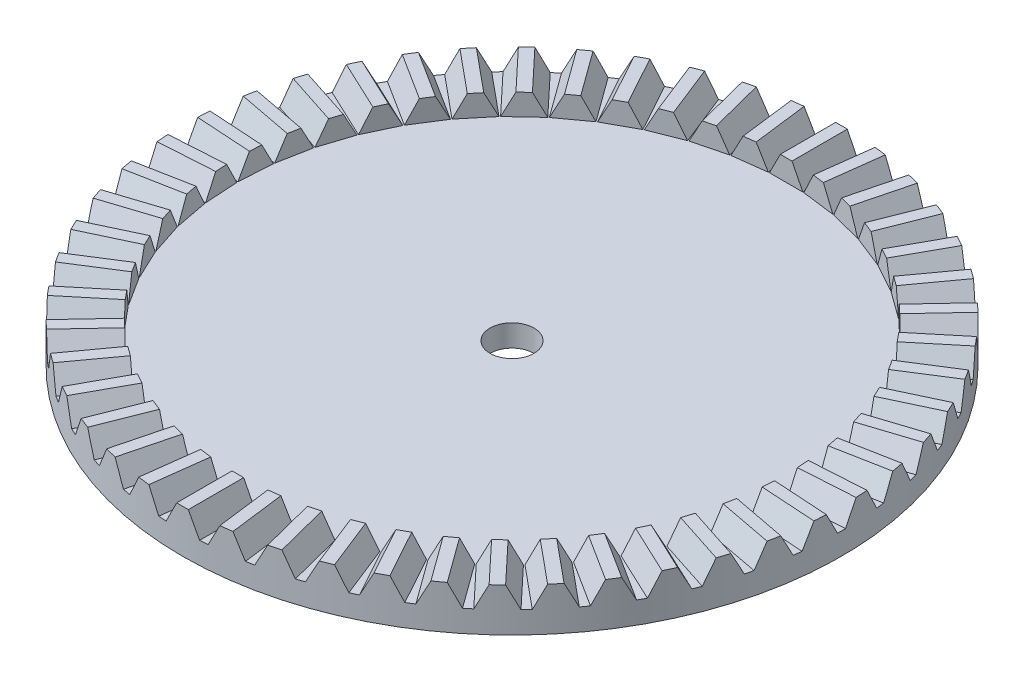
SolidWorks part; units mm, degrees
ref_plane "Front Plane" through (0, 0, 0) normal (0, 0, 1) x (1, 0, 0)
ref_plane "Top Plane" through (0, 0, 0) normal (0, 1, 0) x (1, 0, 0)
ref_plane "Right Plane" through (0, 0, 0) normal (1, 0, 0) x (0, 0, -1)
sketch "Foot Measurements" [suppressed] plane through (0, 0, 0) normal (0, 1, 0) x (1, 0, 0)
  line L0 (0, 0) -> (0, 73) construction
  line L1 (0, 0) -> (0, 147) construction
  line L2 (0, 0) -> (33, 0) construction
  line L3 (0, 0) -> (75, 0) construction
  line L4 (0, 73) -> (33, 73) construction
  line L5 (33, 73) -> (33, 0) construction
  line L6 (0, 147) -> (75, 147) construction
  line L7 (75, 147) -> (75, 0) construction
  line L8 (0, -100) -> (250, -100) construction
  line L9 (0, -100) -> (173, -100) construction
  dimension "D1" = 33
  dimension "D2" = 75
  dimension "D3" = 73
  dimension "D4" = 147
sketch "Sketch3" plane through (0, 0, 0) normal (0, 1, 0) x (1, 0, 0)
  circle A0 centre (0, 0) radius 30
extrude "Boss-Extrude3" add sketch "Sketch3" along normal blind 2
sketch "Sketch6" plane through (0, 2, 0) normal (0, 1, 0) x (1, 0, 0)
  circle A1 centre (0, 0) radius 2
  dimension "D1" = 4
extrude "Cut-Extrude1" cut sketch "Sketch6" against normal up to next
sketch "Sketch5" plane through (0, 2, 0) normal (0, 1, 0) x (1, 0, 0)
  line L3 (-1.5701, 29.9589) -> (-1.5701, 24.9589)
  line L4 (0, 0) -> (-1.5701, 29.9589) construction
  line L5 (0, 0) -> (1.5701, 29.9589) construction
  line L6 (-1.5701, 24.9589) -> (1.5701, 24.9589)
  line L7 (1.5701, 24.9589) -> (1.5701, 29.9589)
  arc A0 (1.5701, 29.9589) -> (-1.5701, 29.9589) centre (0, 0) ccw
  dimension "D2" = 5
  dimension "D1" = 6
  dimension "D3" = 3.1402
extrude "Boss-Extrude5" add sketch "Sketch5" along normal blind 3
sketch "Sketch14" plane through (0, 0, -24.9589) normal (0, 0, 1) x (1, 0, 0)
  line L1 (-1.5701, 2) -> (-1.5701, 5)
  line L2 (-1.5701, 5) -> (1.5701, 5)
  line L3 (1.5701, 2) -> (1.5201, 2)
  line L4 (1.5701, 5) -> (1.5701, 2)
  line L5 (1.5201, 2) -> (0.532, 3.95)
  line L6 (-1.5701, 2) -> (-1.5201, 2)
  line L7 (-1.5201, 2) -> (-0.532, 3.95)
  line L10 (0.532, 3.95) -> (-0.532, 3.95)
  dimension "D1" = 1.05
  dimension "D2" = 0.05
  dimension "D3" = 53.742
  dimension "D4" = 1.0381
extrude "Cut-Extrude4" cut sketch "Sketch14" against normal up to next contours L10 L5 L3 L4 L2 L1 L6 L7 region at (0, 4.0032, -24.9589)
pattern_circular "CirPattern2" count 50 over 360 about axis through (0, -0.001, 0) along (0, 1, 0) of "Cut-Extrude4", "Boss-Extrude5"
